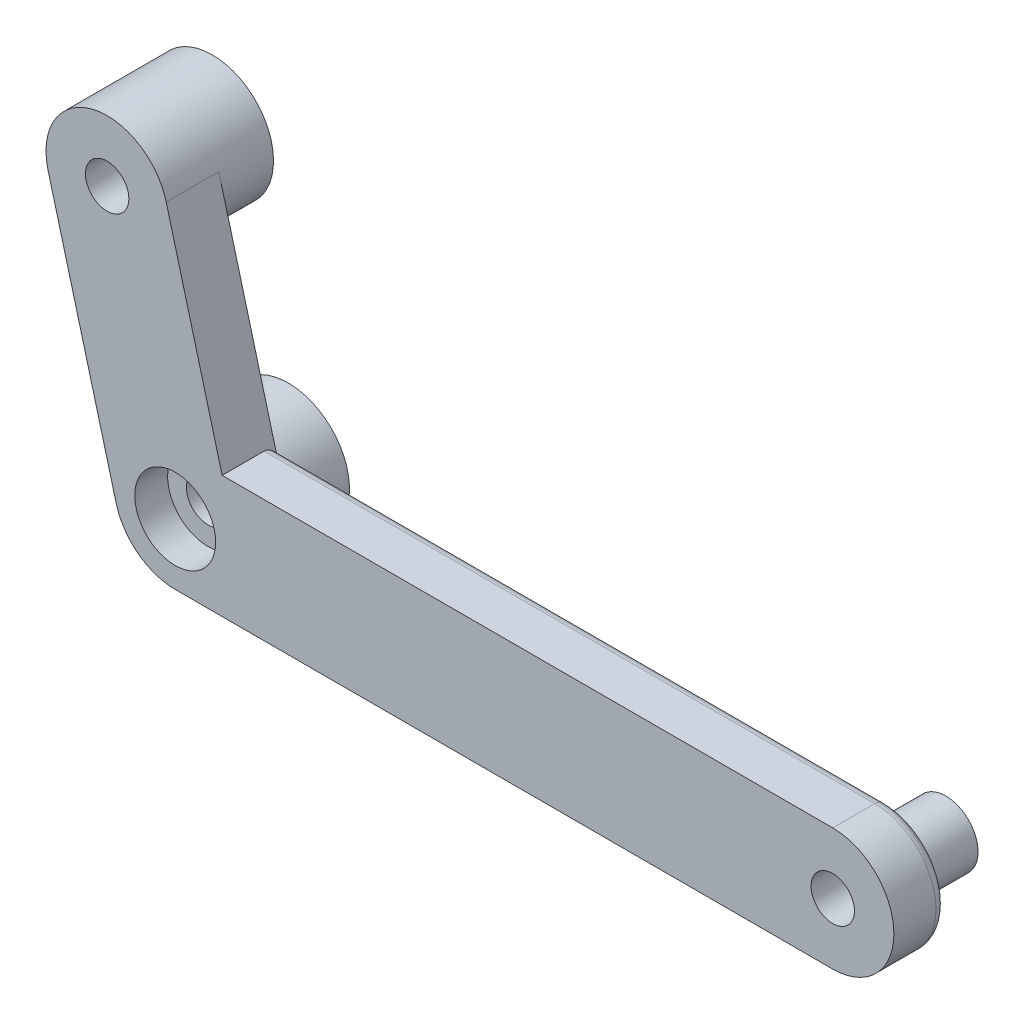
SolidWorks part; units mm, degrees
ref_plane "Front Plane" through (0, 0, 0) normal (0, 0, 1) x (1, 0, 0)
ref_plane "Top Plane" through (0, 0, 0) normal (0, 1, 0) x (1, 0, 0)
ref_plane "Right Plane" through (0, 0, 0) normal (1, 0, 0) x (0, 0, -1)
sketch "Sketch1" plane through (0, 0, 0) normal (0, 0, 1) x (1, 0, 0)
  line L0 (0, 4.65) -> (50, 4.65)
  line L1 (50, -4.65) -> (0, -4.65)
  arc A0 (50, 4.65) -> (50, -4.65) centre (50, 0) cw
  arc A1 (0, -4.65) -> (0, 4.65) centre (0, 0) cw
  circle A2 centre (0, 0) radius 1.65
  circle A3 centre (50, 0) radius 1.65
  dimension "D1" = 3.3
  dimension "D2" = 3
  dimension "D3" = 50
extrude "Boss-Extrude1" add sketch "Sketch1" along normal mid plane 4
sketch "Sketch2" plane through (0, 0, -2) normal (0, 0, -1) x (-1, 0, 0)
  circle A1 centre (-50, 0) radius 1.65 construction
  circle A2 centre (-50, 0) radius 1.65
  circle A3 centre (-50, 0) radius 3.5
  dimension "D1" = 7
extrude "Boss-Extrude2" add sketch "Sketch2" along normal blind 0.4
sketch "Sketch3" plane through (0, 0, -2.4) normal (0, 0, -1) x (-1, 0, 0)
  circle A0 centre (-50, 0) radius 2.45
  circle A1 centre (-50, 0) radius 1.65 construction
  circle A2 centre (-50, 0) radius 1.65
  dimension "D1" = 4.9
extrude "Boss-Extrude3" add sketch "Sketch3" along normal blind 4.2
sketch "Sketch4" plane through (0, 0, 2) normal (0, 0, 1) x (1, 0, 0)
  circle A0 centre (0, 0) radius 3.075
  dimension "D1" = 6.15
extrude "Cut-Extrude1" cut sketch "Sketch4" against normal blind 2.5
sketch "Sketch6" plane through (0, 0, -2) normal (0, 0, -1) x (-1, 0, 0)
  circle A0 centre (0, 0) radius 1.65 construction
  circle A1 centre (0, 0) radius 1.65
  circle A2 centre (0, 0) radius 4.65
  arc A3 (0, -4.65) -> (0, 4.65) centre (0, 0) ccw construction
extrude "Boss-Extrude4" add sketch "Sketch6" along normal up to surface (4.6 mm away) up to face at (47.55, 0, -6.6)
sketch "Sketch8" plane through (0, 0, 2) normal (0, 0, 1) x (1, 0, 0)
  line L0 (50, 0) -> (0, 0) construction
  line L1 (0, 0) -> (-5.1764, 19.3185) construction
  line L4 (-9.6679, 18.115) -> (-4.4916, -1.2035)
  line L6 (-9.6679, 18.115) -> (-0.6848, 20.522) construction
  line L9 (0, 4.65) -> (3.5681, 4.65)
  line L10 (50, 4.65) -> (0, 4.65) construction
  line L11 (3.5681, 4.65) -> (-0.6848, 20.522)
  arc A1 (-9.6679, 18.115) -> (-0.6848, 20.522) centre (-5.1764, 19.3185) cw
  arc A2 (0, 4.65) -> (0, -4.65) centre (0, 0) ccw construction
  arc A3 (0, 4.65) -> (-4.4916, -1.2035) centre (0, 0) ccw
  circle A4 centre (-5.1764, 19.3185) radius 1.65
  dimension "D1" = 3.3
  dimension "D2" = 20
  dimension "D3" = 105
extrude "Boss-Extrude5" add sketch "Sketch8" against normal up to surface (4 mm away) up to face at (46.5, 0, -2)
sketch "Sketch9" [suppressed] plane through (0, 0, 2) normal (0, 0, 1) x (1, 0, 0)
  line L0 (0, 0) -> (-5.1764, -19.3185) construction
  line L1 (3.5681, -4.65) -> (-0.6848, -20.522)
  line L2 (0, -4.65) -> (50, -4.65) construction
  line L3 (-9.6679, -18.115) -> (-4.4916, 1.2035)
  line L4 (0, -4.65) -> (3.5681, -4.65)
  line L5 (-9.6679, -18.115) -> (-0.6848, -20.522) construction
  line L6 (50, 0) -> (0, 0) construction
  arc A0 (-0.6848, -20.522) -> (-9.6679, -18.115) centre (-5.1764, -19.3185) cw
  arc A1 (0, 4.65) -> (0, -4.65) centre (0, 0) ccw construction
  arc A2 (-4.4916, 1.2035) -> (0, -4.65) centre (0, 0) ccw
  circle A3 centre (-5.1764, -19.3185) radius 1.65
  point P1 (-5.1764, -19.3185)
  dimension "D3" = 3.3
  dimension "D1" = 105
  dimension "D2" = 20
extrude "Boss-Extrude6" [suppressed] add sketch "Sketch9" against normal up to surface (4 mm away)
fillet "Fillet1" radius 0.8 3 edges at (26.784, 4.65, -2) (54.65, 0, -2) (25, -4.65, -2)
sketch "Sketch10" [suppressed] plane through (0, 0, -2) normal (0, 0, -1) x (-1, 0, 0)
  circle A0 centre (5.1764, -19.3185) radius 1.65 construction
  circle A1 centre (5.1764, -19.3185) radius 1.65
  circle A2 centre (5.1764, -19.3185) radius 4.65
  arc A3 (0.6848, -20.522) -> (9.6679, -18.115) centre (5.1764, -19.3185) ccw construction
extrude "Boss-Extrude7" [suppressed] add sketch "Sketch10" along normal blind 4
sketch "Sketch11" plane through (0, 0, -2) normal (0, 0, -1) x (-1, 0, 0)
  circle A0 centre (5.1764, 19.3185) radius 1.65 construction
  circle A1 centre (5.1764, 19.3185) radius 1.65
  circle A2 centre (5.1764, 19.3185) radius 4.65
  arc A3 (9.6679, 18.115) -> (0.6848, 20.522) centre (5.1764, 19.3185) ccw construction
extrude "Boss-Extrude8" add sketch "Sketch11" along normal blind 4
sketch "Sketch12" plane through (0, 0, -6) normal (0, 0, -1) x (-1, 0, 0)
  circle A0 centre (5.1764, 19.3185) radius 1.65 construction
  circle A1 centre (5.1764, 19.3185) radius 1.65 construction
  circle A2 centre (5.1764, 19.3185) radius 2.1
  dimension "D1" = 4.2
extrude "Cut-Extrude2" cut sketch "Sketch12" against normal blind 5
sketch "Sketch13" [suppressed] plane through (0, 0, 2) normal (0, 0, 1) x (1, 0, 0)
  circle A0 centre (-5.1764, -19.3185) radius 3
  dimension "D1" = 6
extrude "Cut-Extrude3" [suppressed] cut sketch "Sketch13" against normal blind 4
